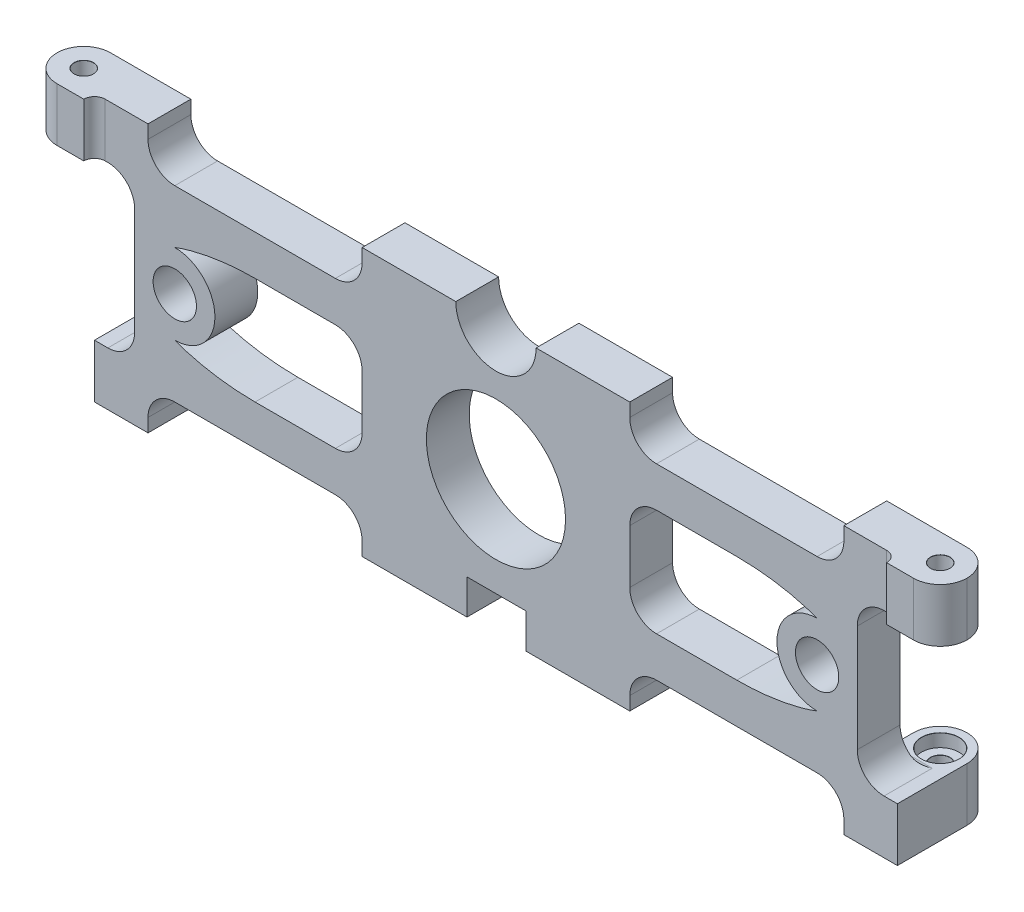
SolidWorks part; units mm, degrees
ref_plane "Front" through (0, 0, 0) normal (0, 0, 1) x (1, 0, 0)
ref_plane "Top" through (0, 0, 0) normal (0, 1, 0) x (1, 0, 0)
ref_plane "Right" through (0, 0, 0) normal (1, 0, 0) x (0, 0, -1)
sketch "Эскиз1" plane through (0, 0, 0) normal (0, 0, 1) x (1, 0, 0)
  line L1 (-75, -25) -> (75, -25)
  line L2 (-75, -25) -> (-75, 25)
  line L3 (-75, 25) -> (75, 25)
  line L4 (75, -25) -> (75, 25)
  line L5 (-75, -25) -> (75, 25) construction
  line L6 (-75, 25) -> (75, -25) construction
  point P0 (0, 0)
extrude "Бобышка-Вытянуть1" add sketch "Эскиз1" along normal blind 8 contours L3 L4 L1 L2
sketch "Эскиз5" plane through (0, 0, 8) normal (0, 0, 1) x (1, 0, 0)
  line L6 (-75, 25) -> (75, -25) construction
  line L7 (75, 25) -> (-75, -25) construction
  circle A0 centre (0, 0) radius 13
extrude "Вырез-Вытянуть5" cut sketch "Эскиз5" against normal through all
sketch "Эскиз6" plane through (0, 0, 8) normal (0, 0, 1) x (1, 0, 0)
  line L0 (0, 35.2364) -> (0, -37.6455) construction
  line L1 (-81.5914, 0) -> (80.5963, 0) construction
  circle A0 centre (-60, 0) radius 4.05
  circle A1 centre (60, 0) radius 4.05
  dimension "D1" = 60
  dimension "D3" = 8.1
  dimension "D4" = 8.1
  dimension "D2" = 120
extrude "Вырез-Вытянуть6" cut sketch "Эскиз6" against normal through all
sketch "Эскиз7" plane through (0, 0, 8) normal (0, 0, 1) x (1, 0, 0)
  line L1 (-65, -25) -> (-25, -25)
  line L2 (0, -44.0947) -> (0, 37.2264) construction
  line L3 (-80.4974, 0) -> (82.7196, 0) construction
  line L4 (-65, -25) -> (-65, -22.5)
  line L5 (-75, -25) -> (75, -25) construction
  line L6 (-60, -17.5) -> (-30, -17.5)
  line L7 (-25, -22.5) -> (-25, -25)
  line L8 (-75, -25) -> (-75, 25) construction
  line L9 (-75, -15) -> (-72.5, -15)
  line L10 (-67.5, -10) -> (-67.5, 10)
  line L11 (-72.5, 15) -> (-75, 15)
  line L12 (-75, 15) -> (-75, -15)
  line L13 (-75, 25) -> (75, 25) construction
  line L14 (-25, 22.5) -> (-25, 25)
  line L15 (-60, 17.5) -> (-30, 17.5)
  line L16 (-65, 25) -> (-65, 22.5)
  line L17 (-65, 25) -> (-25, 25)
  line L18 (65, 25) -> (25, 25)
  line L19 (65, 25) -> (65, 22.5)
  line L20 (60, 17.5) -> (30, 17.5)
  line L21 (25, 22.5) -> (25, 25)
  line L22 (75, 15) -> (75, -15)
  line L23 (72.5, 15) -> (75, 15)
  line L24 (67.5, -10) -> (67.5, 10)
  line L25 (75, -15) -> (72.5, -15)
  line L26 (25, -22.5) -> (25, -25)
  line L27 (60, -17.5) -> (30, -17.5)
  line L28 (65, -25) -> (65, -22.5)
  line L29 (65, -25) -> (25, -25)
  line L30 (-7.5, 25) -> (7.5, 25)
  arc A0 (-25, -22.5) -> (-30, -17.5) centre (-30, -22.5) ccw
  arc A1 (-60, -17.5) -> (-65, -22.5) centre (-60, -22.5) ccw
  arc A3 (7.5, 25) -> (-7.5, 25) centre (0, 25) cw
  arc A4 (-72.5, 15) -> (-67.5, 10) centre (-72.5, 10) cw
  arc A5 (-67.5, -10) -> (-72.5, -15) centre (-72.5, -10) cw
  arc A6 (-60, 17.5) -> (-65, 22.5) centre (-60, 22.5) cw
  arc A7 (-25, 22.5) -> (-30, 17.5) centre (-30, 22.5) cw
  arc A8 (25, 22.5) -> (30, 17.5) centre (30, 22.5) ccw
  arc A9 (60, 17.5) -> (65, 22.5) centre (60, 22.5) ccw
  arc A10 (67.5, -10) -> (72.5, -15) centre (72.5, -10) ccw
  arc A11 (72.5, 15) -> (67.5, 10) centre (72.5, 10) ccw
  arc A12 (60, -17.5) -> (65, -22.5) centre (60, -22.5) cw
  arc A13 (25, -22.5) -> (30, -17.5) centre (30, -22.5) cw
  point P15 (-25, -17.5)
  point P18 (-65, -17.5)
  point P30 (-67.5, 15)
  point P33 (-67.5, -15)
  point P42 (-65, 17.5)
  point P43 (-25, 17.5)
  point P68 (25, 17.5)
  point P69 (65, 17.5)
  point P70 (67.5, -15)
  point P71 (67.5, 15)
  point P72 (65, -17.5)
  point P73 (25, -17.5)
  dimension "D3" = 5
  dimension "D4" = 5
  dimension "D5" = 7.5
  dimension "D9" = 5
  dimension "D10" = 5
  dimension "D1" = 10
  dimension "D2" = 40
  dimension "D6" = 10
  dimension "D7" = 30
  dimension "D8" = 10
extrude "Вырез-Вытянуть7" cut sketch "Эскиз7" against normal through all
sketch "Эскиз8" plane through (0, 0, 0) normal (0, 0, -1) x (-1, 0, 0)
  line L0 (-78.922, 0) -> (76.8097, 0) construction
  line L1 (0, -33.7328) -> (0, 41.5826) construction
  line L2 (25, -5) -> (25, 5)
  line L3 (45, 10) -> (30, 10)
  line L4 (-45, -10) -> (-30, -10)
  line L5 (45, -10) -> (30, -10)
  line L6 (30, -17.5) -> (60, -17.5) construction
  line L7 (-45, 10) -> (-30, 10)
  line L8 (-25, -5) -> (-25, 5)
  arc A0 (60, 7.5) -> (60, -7.5) centre (60, 0) ccw
  arc A1 (25, -5) -> (30, -10) centre (30, -5) ccw
  arc A2 (25, 5) -> (30, 10) centre (30, 5) cw
  arc A3 (-25, 5) -> (-30, 10) centre (-30, 5) ccw
  arc A4 (-25, -5) -> (-30, -10) centre (-30, -5) cw
  arc A5 (-60, 7.5) -> (-60, -7.5) centre (-60, 0) cw
  spline S0 degree 3 poles (60, -7.5) (59.9555, -7.5) (54.1279, -10) (45, -10) knots 0 0 0 0 1 1 1 1
  spline S1 degree 3 poles (60, 7.5) (59.9555, 7.5) (54.1279, 10) (45, 10) knots 0 0 0 0 1 1 1 1
  spline S2 degree 3 poles (-60, 7.5) (-59.9555, 7.5) (-54.1279, 10) (-45, 10) knots 0 0 0 0 1 1 1 1
  spline S3 degree 3 poles (-60, -7.5) (-59.9555, -7.5) (-54.1279, -10) (-45, -10) knots 0 0 0 0 1 1 1 1
  point P11 (25, 0)
  point P31 (-25, 0)
  dimension "D1" = 7.5
  dimension "D2" = 5
extrude "Вырез-Вытянуть8" cut sketch "Эскиз8" against normal through all
sketch "Эскиз17" plane through (75, 0, 0) normal (1, 0, 0) x (0, 0, -1)
  line L1 (0, 15) -> (-10, 15)
  line L2 (0, 15) -> (0, 25)
  line L3 (0, 25) -> (-10, 25)
  line L4 (-10, 15) -> (-10, 25)
extrude "Бобышка-Вытянуть3" add sketch "Эскиз17" along normal blind 10
sketch "Эскиз18" plane through (-75, 0, 0) normal (-1, 0, 0) x (0, 0, 1)
  line L0 (10, 15) -> (8, 15) construction
  line L1 (0, 25) -> (10, 25)
  line L2 (0, 25) -> (0, 15)
  line L3 (0, 15) -> (10, 15)
  line L4 (10, 25) -> (10, 15)
extrude "Бобышка-Вытянуть4" add sketch "Эскиз18" along normal blind 10
fillet "Скругление2" radius 5 4 edges at (85, 20, 0) (85, 20, 10) (-85, 20, 0) (-85, 20, 10)
fillet "Скругление3" radius 2 2 edges at (75, 20, 8) (-75, 20, 8)
hole_wizard "Цековка для винта с заклепочной головкой M31" positions "Трехмерный эскиз2" profile "Эскиз19" counterbore size "M3" standard "Ansi Metric" end condition through all
sketch3d "Трехмерный эскиз2"
  line L0 (80, 15, 5) -> (80, 25, 5) construction
  point P0 (80, 15, 5)
sketch "Эскиз19" plane through (80, 15, 5) normal (1, 0, 0) x (0, 0, -1)
  line L0 (0, 0) -> (0, 10)
  line L1 (1.8, 9.975) -> (1.825, 10)
  line L2 (1.8, 9.975) -> (1.8, 2.425)
  line L3 (1.8, 2.425) -> (1.825, 2.4)
  line L4 (1.825, 2.4) -> (3.5, 2.4)
  line L5 (3.5, 2.4) -> (3.5, 0.025)
  line L6 (3.5, 0.025) -> (3.525, 0)
  line L7 (3.525, 0) -> (0, 0)
  line L8 (-3.5, 0.025) -> (-3.525, 0) construction
  line L9 (-1.8, 2.425) -> (-1.825, 2.4) construction
  line L11 (0, -6.35) -> (0, 107.95) construction
  line L12 (1.825, 10) -> (0, 10)
  line L13 (-1.8, 9.975) -> (-1.825, 10) construction
  dimension "Диаметр сквозного отверстия" = 3.6
  dimension "Глубина сквозного отверстия" = 10
  dimension "Диаметр цековки" = 7
  dimension "Глубина цековки" = 2.4
  dimension "Диаметр передней зенковки" = 7.05
  dimension "Угол передней зенковки" = 90
  dimension "Диаметр средней зенковки" = 3.65
  dimension "Угол средней зенковки" = 90
  dimension "Диаметр задней зенковки" = 3.65
  dimension "Угол задней зенковки" = 90
hole_wizard "Цековка для винта с заклепочной головкой M32" positions "Трехмерный эскиз3" profile "Эскиз20" counterbore size "M3" standard "Ansi Metric" end condition through all
sketch3d "Трехмерный эскиз3"
  line L0 (-80, 25, 5) -> (-80, 15, 5) construction
  point P0 (-80, 15, 5)
sketch "Эскиз20" plane through (-80, 15, 5) normal (1, 0, 0) x (0, 0, -1)
  line L0 (0, 0) -> (0, 10)
  line L1 (1.8, 9.975) -> (1.825, 10)
  line L2 (1.8, 9.975) -> (1.8, 2.425)
  line L3 (1.8, 2.425) -> (1.825, 2.4)
  line L4 (1.825, 2.4) -> (3.5, 2.4)
  line L5 (3.5, 2.4) -> (3.5, 0.025)
  line L6 (3.5, 0.025) -> (3.525, 0)
  line L7 (3.525, 0) -> (0, 0)
  line L8 (-3.5, 0.025) -> (-3.525, 0) construction
  line L9 (-1.8, 2.425) -> (-1.825, 2.4) construction
  line L11 (0, -6.35) -> (0, 107.95) construction
  line L12 (1.825, 10) -> (0, 10)
  line L13 (-1.8, 9.975) -> (-1.825, 10) construction
  dimension "Диаметр сквозного отверстия" = 3.6
  dimension "Глубина сквозного отверстия" = 10
  dimension "Диаметр цековки" = 7
  dimension "Глубина цековки" = 2.4
  dimension "Диаметр передней зенковки" = 7.05
  dimension "Угол передней зенковки" = 90
  dimension "Диаметр средней зенковки" = 3.65
  dimension "Угол средней зенковки" = 90
  dimension "Диаметр задней зенковки" = 3.65
  dimension "Угол задней зенковки" = 90
sketch "Эскиз26" plane through (0, 0, 0) normal (0, 0, -1) x (-1, 0, 0)
  line L1 (-75, -25) -> (-65, -25)
  line L2 (-75, -25) -> (-75, -15)
  line L3 (-75, -15) -> (-65, -15)
  line L4 (-65, -25) -> (-65, -15)
  line L5 (75, -25) -> (65, -25)
  line L6 (75, -25) -> (75, -15)
  line L7 (75, -15) -> (65, -15)
  line L8 (65, -25) -> (65, -15)
extrude "Бобышка-Вытянуть6" add sketch "Эскиз26" along normal blind 10
fillet "Скругление8" radius 1 4 edges at (65, -18.75, 0) (68.75, -15, 0) (-68.75, -15, 0) (-65, -18.75, 0)
fillet "Скругление9" radius 5 4 edges at (75, -20, -10) (65, -20, -10) (-65, -20, -10) (-75, -20, -10)
hole_wizard "Цековка для винта с заклепочной головкой M33" positions "Трехмерный эскиз5" profile "Эскиз29" counterbore size "M3" standard "Ansi Metric" end condition through all
sketch3d "Трехмерный эскиз5"
  line L0 (-70, -25, -5) -> (-70, -15, -5) construction
  line L1 (70, -15, -5) -> (70, -25, -5) construction
  point P0 (-70, -15, -5)
  point P4 (70, -15, -5)
sketch "Эскиз29" plane through (-70, -15, -5) normal (1, 0, 0) x (0, 0, 1)
  line L0 (0, 0) -> (0, 10)
  line L1 (1.8, 9.975) -> (1.825, 10)
  line L2 (1.8, 9.975) -> (1.8, 2.425)
  line L3 (1.8, 2.425) -> (1.825, 2.4)
  line L4 (1.825, 2.4) -> (3.5, 2.4)
  line L5 (3.5, 2.4) -> (3.5, 0.025)
  line L6 (3.5, 0.025) -> (3.525, 0)
  line L7 (3.525, 0) -> (0, 0)
  line L8 (-3.5, 0.025) -> (-3.525, 0) construction
  line L9 (-1.8, 2.425) -> (-1.825, 2.4) construction
  line L11 (0, -6.35) -> (0, 107.95) construction
  line L12 (1.825, 10) -> (0, 10)
  line L13 (-1.8, 9.975) -> (-1.825, 10) construction
  dimension "Диаметр сквозного отверстия" = 3.6
  dimension "Глубина сквозного отверстия" = 10
  dimension "Диаметр цековки" = 7
  dimension "Глубина цековки" = 2.4
  dimension "Диаметр передней зенковки" = 7.05
  dimension "Угол передней зенковки" = 90
  dimension "Диаметр средней зенковки" = 3.65
  dimension "Угол средней зенковки" = 90
  dimension "Диаметр задней зенковки" = 3.65
  dimension "Угол задней зенковки" = 90
sketch "Эскиз30" plane through (0, -25, 0) normal (0, -1, 0) x (1, 0, 0)
  line L0 (25, 0) -> (-25, 8) construction
  line L1 (-25, 0) -> (25.1872, 8) construction
  line L2 (-25, 8) -> (25, 8) construction
  line L4 (-5.4064, 0) -> (5.5936, 0)
  line L5 (-5.4064, 0) -> (-5.4064, 8)
  line L6 (-5.4064, 8) -> (5.5936, 8)
  line L7 (5.5936, 0) -> (5.5936, 8)
  line L8 (-5.4064, 0) -> (5.5936, 8) construction
  line L9 (-5.4064, 8) -> (5.5936, 0) construction
  point P10 (0.0936, 4)
  dimension "D1" = 11
extrude "Вырез-Вытянуть9" cut sketch "Эскиз30" against normal blind 6.5
